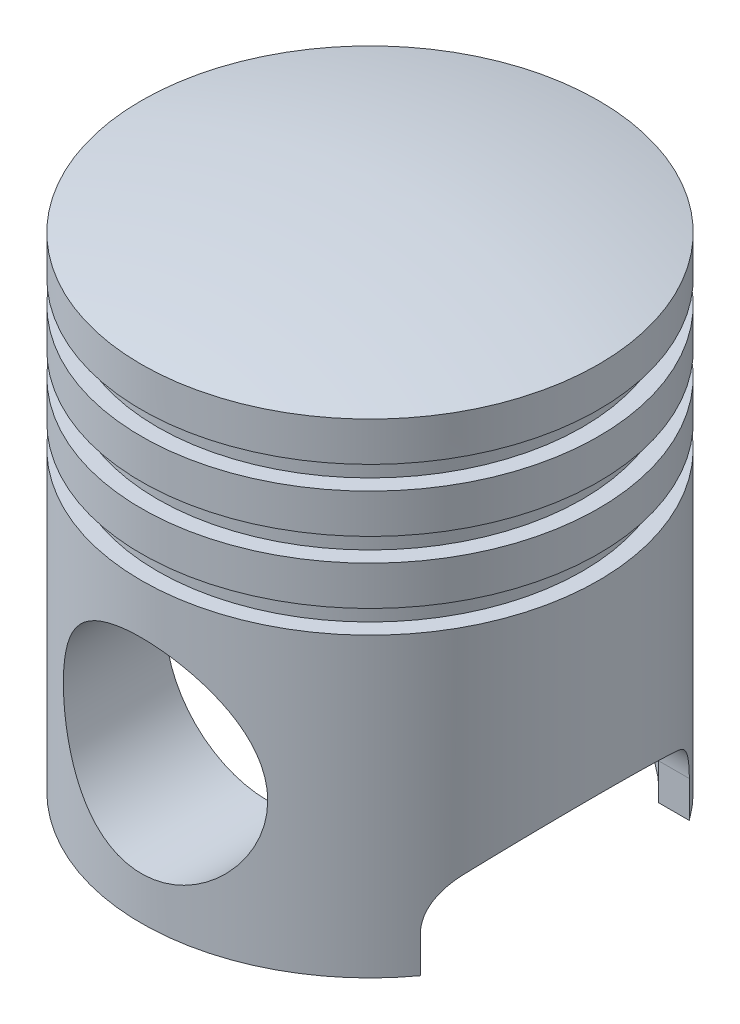
SolidWorks part; units mm, degrees
material "1060 Alloy"
ref_plane "Front Plane" through (0, 0, 0) normal (0, 0, 1) x (1, 0, 0)
ref_plane "Top Plane" through (0, 0, 0) normal (0, 1, 0) x (1, 0, 0)
ref_plane "Right Plane" through (0, 0, 0) normal (1, 0, 0) x (0, 0, -1)
sketch "Sketch1" plane through (0, 0, 0) normal (0, 1, 0) x (1, 0, 0)
  circle A0 centre (0, 0) radius 42.5
  dimension "D1" = 85
extrude "Boss-Extrude1" add sketch "Sketch1" along normal blind 90
sketch "Sketch3" plane through (0, 90, 0) normal (0, 1, 0) x (1, 0, 0)
  circle A0 centre (0, 0) radius 39.5
  dimension "D1" = 79
extrude "Cut-Extrude17" cut sketch "Sketch3" against normal blind 4.3 from offset 7.3 flip side to cut offset against normal yes
pattern_linear "LPattern2" count 3 spacing 11.6 along (0, -1, 0) of "Cut-Extrude17"
sketch "Sketch4" plane through (0, 0, 0) normal (0, -1, 0) x (1, 0, 0)
  circle A0 centre (0, 0) radius 38
  dimension "D1" = 76
extrude "Cut-Extrude18" cut sketch "Sketch4" against normal blind 85
dome "Dome1" faces to dome 1 distance 5 reverse direction no elliptical dome no face at (0, 90, 42.5) parameters "D1"=5
sketch "Sketch5" plane through (0, 0, 0) normal (0, 0, 1) x (1, 0, 0)
  line L0 (0, 55.2) -> (0, 0) construction
  line L1 (-42.5, 0) -> (42.5, 0) construction
  circle A0 centre (0, 27) radius 19
  dimension "D1" = 38
  dimension "D2" = 27
extrude "Cut-Extrude20" cut sketch "Sketch5" against normal through all both and the other way through all
sketch "Sketch6" plane through (0, 0, 0) normal (1, 0, 0) x (0, 0, -1)
  line L0 (0, 0) -> (0, 55.2) construction
  line L1 (42.5, 55.2) -> (-42.5, 55.2) construction
  line L2 (-25, 0) -> (-25, 12)
  line L3 (-42.5, 0) -> (42.5, 0) construction
  line L4 (25, 0) -> (25, 12)
  arc A0 (-25, 12) -> (25, 12) centre (0, -19.225) cw
  point P12 (0, 20.775)
  dimension "D2" = 40
  dimension "D1" = 50
extrude "Cut-Extrude21" cut sketch "Sketch6" against normal through all both and the other way through all
fillet "Fillet1" radius 10 4 edges at (-31.4937, 12, -25) (31.4937, 12, -25) (-31.4937, 12, 25) (31.4937, 12, 25)
sketch "Sketch7" plane through (0, 0, 0) normal (0, 0, 1) x (1, 0, 0)
  circle A0 centre (0, 27) radius 22.5
  circle A1 centre (0, 27) radius 19 construction
  circle A2 centre (0, 27) radius 19
  dimension "D1" = 45
extrude "Boss-Extrude3" add sketch "Sketch7" along normal up to next from offset 19
mirror "Mirror1" about plane through (0, 0, 0) normal (0, 0, 1) of "Boss-Extrude3"
